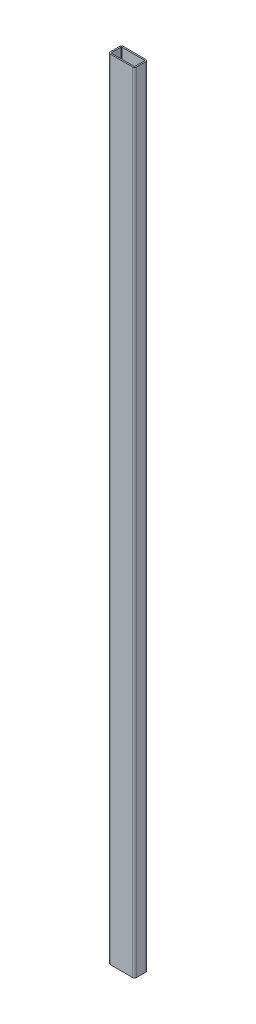
SolidWorks part; units mm, degrees
ref_plane "Спереди" through (0, 0, 0) normal (0, 0, 1) x (1, 0, 0)
ref_plane "Сверху" through (0, 0, 0) normal (0, 1, 0) x (1, 0, 0)
ref_plane "Справа" through (0, 0, 0) normal (1, 0, 0) x (0, 0, -1)
sketch "Эскиз1" plane through (0, 0, 0) normal (0, 1, 0) x (1, 0, 0)
  line L1 (3, 0) -> (37, 0)
  line L2 (0, 3) -> (0, 17)
  line L3 (3, 20) -> (37, 20)
  line L4 (40, 3) -> (40, 17)
  arc A0 (37, 0) -> (40, 3) centre (37, 3) ccw
  arc A1 (40, 17) -> (37, 20) centre (37, 17) ccw
  arc A2 (0, 17) -> (3, 20) centre (3, 17) cw
  arc A3 (0, 3) -> (3, 0) centre (3, 3) ccw
  point P13 (0, 0)
  dimension "D1" = 3
extrude "Вытянуть-Тонкостенный1" add sketch "Эскиз1" along normal blind 1200 thin thin type one direction reverse wall 2
